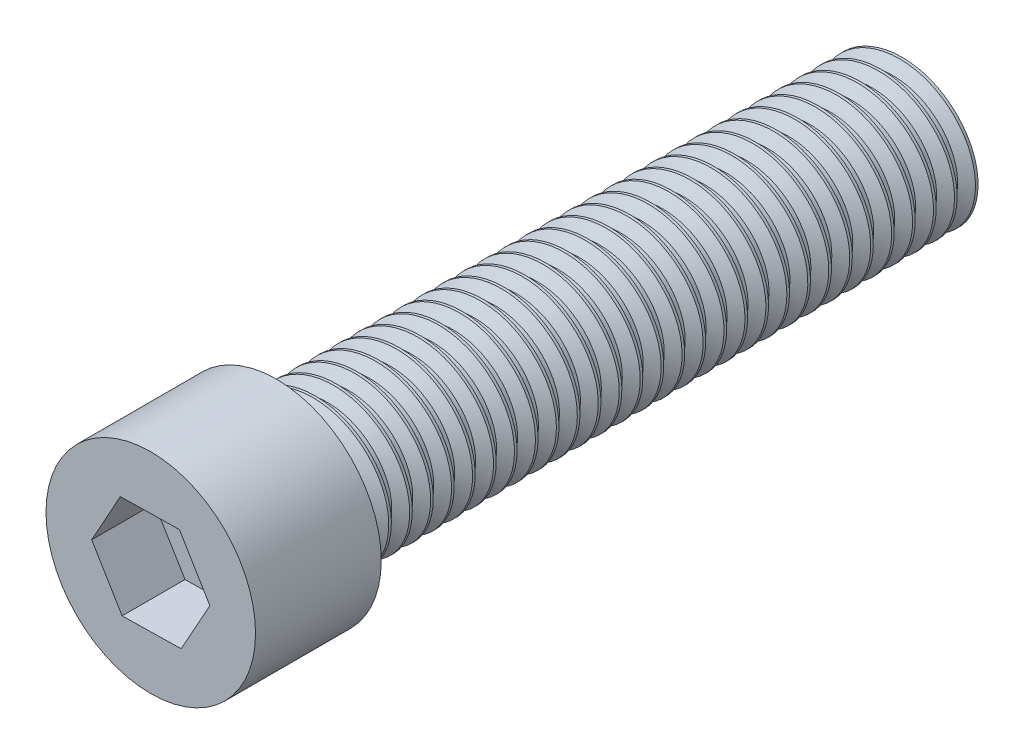
SolidWorks part; units mm, degrees
ref_plane "Front Plane" through (0, 0, 0) normal (0, 0, 1) x (1, 0, 0)
ref_plane "Top Plane" through (0, 0, 0) normal (0, 1, 0) x (1, 0, 0)
ref_plane "Right Plane" through (0, 0, 0) normal (1, 0, 0) x (0, 0, -1)
sketch "Sketch1" plane through (0, 0, 0) normal (0, 0, 1) x (1, 0, 0)
  circle A0 centre (0, 0) radius 1.5
  dimension "D1" = 3
extrude "Boss-Extrude1" add sketch "Sketch1" along normal blind 15
thread "Thread1" pitch 0.5 method extrude profile "Thread Profile1" start angle 0, offset 0, length 15, pitch 0.5, diameter 3
ref_plane "Plane1" through (-1.5, 0, 15) normal (0, -1, 0) x (-1, 0, 0)
sketch "Thread Profile1" plane through (-1.5, 0, 15) normal (0, -1, 0) x (-1, 0, 0)
  line L0 (0, 0) -> (0, 0.5) construction
  line L1 (0, 0) -> (0.2706, 0.1562)
  line L2 (0.2706, 0.1562) -> (0.2706, 0.2187)
  line L3 (0.2706, 0.2187) -> (0, 0.375)
  line L4 (0.2706, 0.1875) -> (0, 0.1875) construction
  line L11 (0, 0) -> (0, 0.375)
  point P2 (0, 0)
  dimension "Pitch" = 0.5
  dimension "Profile_Angle" = 60
  dimension "Profile_Land" = 0.0625
  dimension "Profile_Height" = 0.2706
sketch "Sketch4" plane through (0, 0, 15) normal (0, 0, 1) x (1, 0, 0)
  circle A0 centre (0, 0) radius 2.5
  dimension "D1" = 5
extrude "Boss-Extrude2" add sketch "Sketch4" along normal blind 3
sketch "Sketch5" plane through (0, 0, 18) normal (0, 0, 1) x (1, 0, 0)
  line L1 (0.7268, -1.2087) -> (1.4102, 0.0251)
  line L2 (1.4102, 0.0251) -> (0.6834, 1.2338)
  line L3 (0.6834, 1.2338) -> (-0.7268, 1.2087)
  line L4 (-0.7268, 1.2087) -> (-1.4102, -0.0251)
  line L5 (-1.4102, -0.0251) -> (-0.6834, -1.2338)
  line L6 (-0.6834, -1.2338) -> (0.7268, -1.2087)
  circle A1 centre (0, 0) radius 1.2214 construction
extrude "Cut-Extrude1" cut sketch "Sketch5" against normal blind 1.5
